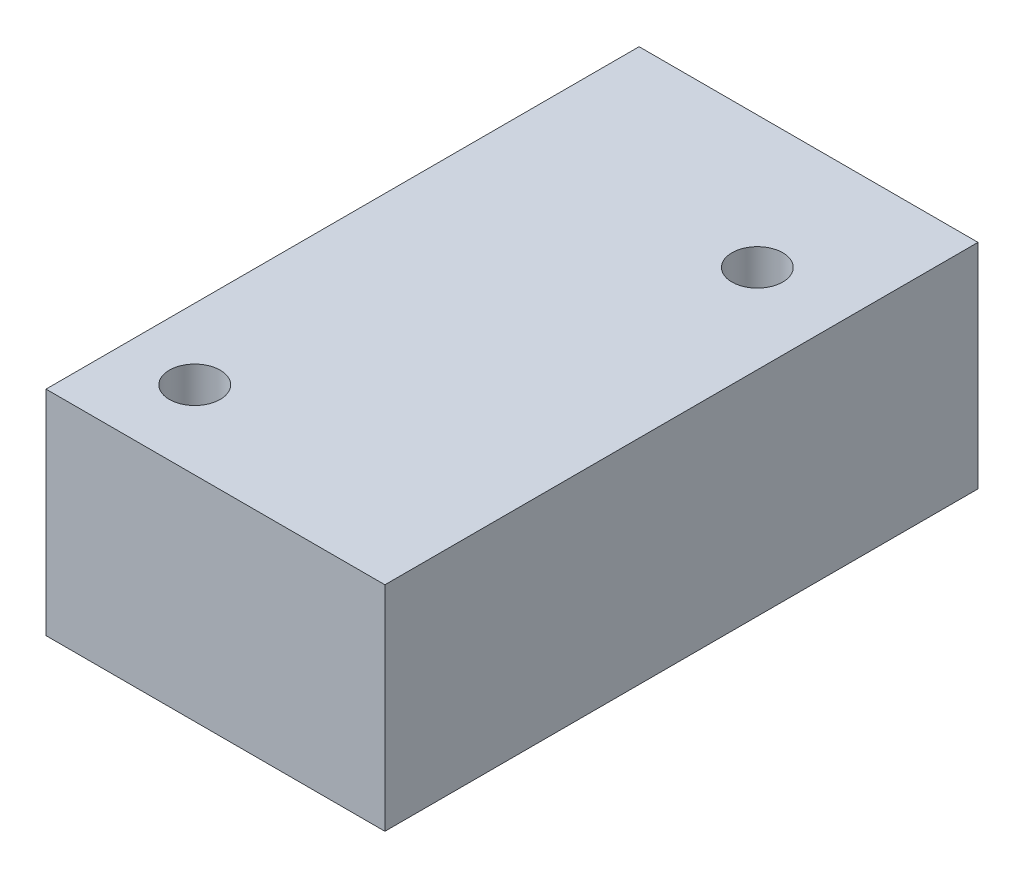
SolidWorks part; units mm, degrees
ref_plane "Front Plane" through (0, 0, 0) normal (0, 0, 1) x (1, 0, 0)
ref_plane "Top Plane" through (0, 0, 0) normal (0, 1, 0) x (1, 0, 0)
ref_plane "Right Plane" through (0, 0, 0) normal (1, 0, 0) x (0, 0, -1)
sketch "Sketch1" plane through (0, 0, 0) normal (0, 1, 0) x (1, 0, 0)
  line L1 (-10, 17.5) -> (10, 17.5)
  line L2 (-10, 17.5) -> (-10, -17.5)
  line L3 (-10, -17.5) -> (10, -17.5)
  line L4 (10, 17.5) -> (10, -17.5)
  line L5 (-10, 17.5) -> (10, -17.5) construction
  line L6 (-10, -17.5) -> (10, 17.5) construction
  point P0 (0, 0)
  dimension "D1" = 20
  dimension "D2" = 35
extrude "Boss-Extrude1" add sketch "Sketch1" along normal blind 12.6
sketch "Sketch2" plane through (0, 0, 0) normal (0, -1, 0) x (1, 0, 0)
  circle A0 centre (-5.8311, 12.8901) radius 1.5 construction
  circle A1 centre (4.7689, -9.7099) radius 1.5 construction
  circle A2 centre (-5.8311, 12.8901) radius 1.5
  circle A3 centre (4.7689, -9.7099) radius 1.5
extrude "Cut-Extrude1" cut sketch "Sketch2" against normal up to next
sketch "Sketch3" plane through (0, 0, 0) normal (0, 1, 0) x (1, 0, 0)
  line L4 (10, -17.5) -> (10, 17.5)
  line L5 (10, 17.5) -> (-10, 17.5)
  line L6 (-10, 17.5) -> (-10, -17.5)
  line L7 (-10, -17.5) -> (10, -17.5)
  line L8 (10, -17.5) -> (10, 17.5)
  line L9 (10, 17.5) -> (-10, 17.5)
  line L10 (-10, 17.5) -> (-10, -17.5)
  line L11 (-10, -17.5) -> (10, -17.5)
  circle A0 centre (4.7689, 9.7099) radius 1.5 construction
  circle A1 centre (-5.8311, -12.8901) radius 1.5 construction
  circle A2 centre (4.7689, 9.7099) radius 1.5
  circle A3 centre (-5.8311, -12.8901) radius 1.5
  dimension "D1" = 0
